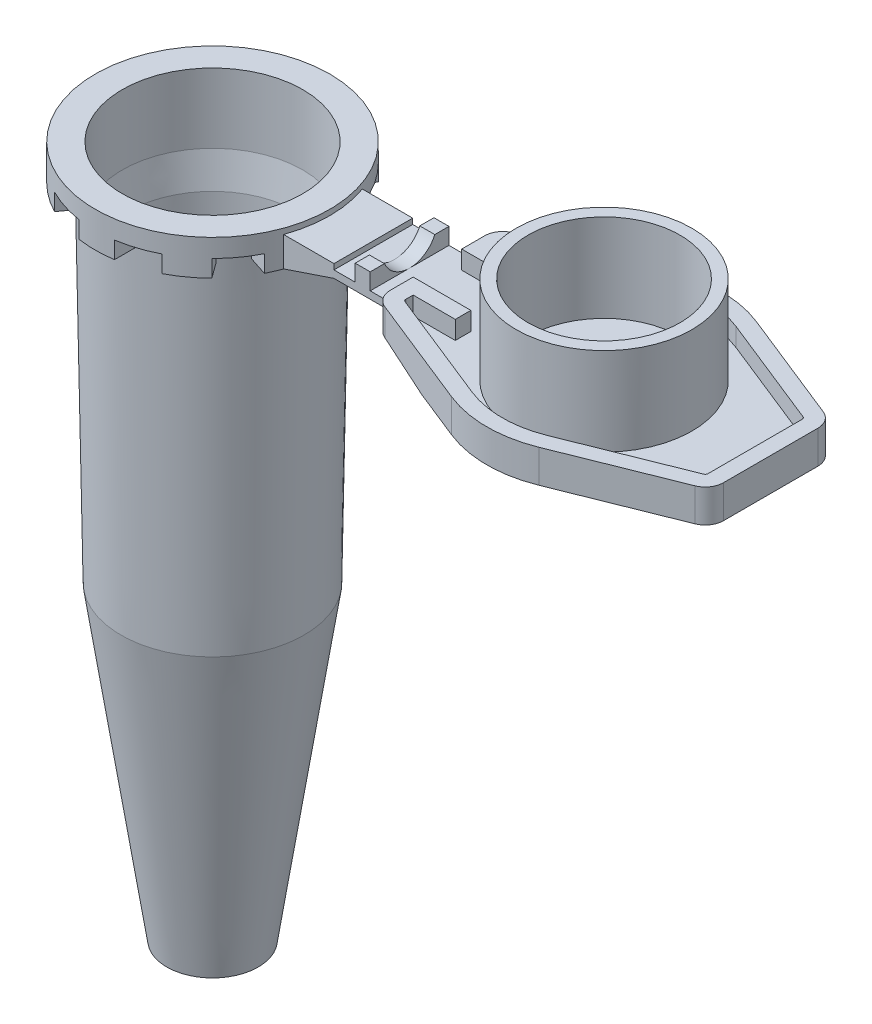
SolidWorks part; units mm, degrees
ref_plane "Front Plane" through (0, 0, 0) normal (0, 0, 1) x (1, 0, 0)
ref_plane "Top Plane" through (0, 0, 0) normal (0, 1, 0) x (1, 0, 0)
ref_plane "Right Plane" through (0, 0, 0) normal (1, 0, 0) x (0, 0, -1)
sketch "Sketch1" plane through (0, 0, 0) normal (0, 0, 1) x (1, 0, 0)
  line L0 (0, 0) -> (0, 43.428) construction
  line L1 (0, 38.64) -> (-6.405, 38.64)
  line L2 (-6.405, 38.64) -> (-6.405, 37.64)
  line L3 (-6.405, 37.64) -> (-5.325, 37.64)
  line L4 (-5.325, 37.64) -> (-5, 17.8)
  line L5 (-5, 17.8) -> (-2.5, 0.85)
  line L7 (0, 38.64) -> (0, 0)
  line L8 (-18.3321, 0.85) -> (18.9529, 0.85) construction
  arc A0 (-2.5, 0.85) -> (0, 0) centre (0, 4.1015) ccw
  point P12 (-2.5, 0.85)
  point P13 (2.5, 0.85)
  dimension "D7" = 5
  dimension "D1" = 38.64
  dimension "D2" = 12.81
  dimension "D3" = 17.8
  dimension "D4" = 10
  dimension "D5" = 10.65
  dimension "D6" = 1
  dimension "D10" = 1.7
revolve "Revolve1" add sketch "Sketch1" angle 360 about L0
sketch "Sketch2" plane through (0, 0, 0) normal (0, 0, 1) x (1, 0, 0)
  line L0 (0, 0.8) -> (0, 41.0311) construction
  line L2 (6.405, 38.64) -> (-6.405, 38.64) construction
  line L3 (-4.6, 33.04) -> (-4.25, 18.44)
  line L5 (0, 38.64) -> (0, 0) construction
  line L7 (-4.25, 18.44) -> (-1.9986, 2.5356)
  line L10 (0, 0.8) -> (4.8244, 0.8) construction
  line L16 (-4.93, 38.64) -> (-4.93, 34.84)
  line L17 (0, 38.64) -> (-6.405, 38.64) construction
  line L19 (0, 0.8) -> (0, 38.64)
  line L20 (0, 38.64) -> (-4.93, 38.64)
  line L21 (-4.6, 33.04) -> (-4.93, 34.84)
  arc A6 (-1.9986, 2.5356) -> (0, 0.8) centre (0, 2.8185) ccw
  point P0 (-3.5705, 13.64)
  point P2 (-4, 16.674)
  point P4 (-1.901, 2.14)
  point P12 (-4.8789, 44.6737)
  dimension "D1" = 9.86
  dimension "D2" = 9.2
  dimension "D3" = 8.5
  dimension "D4" = 0.8
  dimension "D5" = 25
  dimension "D6" = 9.7578
  dimension "D7" = 8
  dimension "D8" = 3.8
  dimension "D9" = 5.6
  dimension "D10" = 20.2
  dimension "D11" = 21.966
  dimension "D12" = 7.141
  dimension "D13" = 36.1044
  dimension "D14" = 36.5
  dimension "D15" = 3.8021
other "AlignGroup1"
revolve "Cut-Revolve1" cut sketch "Sketch2" angle 360 about L0
sketch "Sketch3" plane through (0, 37.64, 0) normal (0, -1, 0) x (1, 0, 0)
  line L0 (-0.975, 6.3304) -> (-0.975, 5.235)
  line L1 (0, 0) -> (0, 7.664) construction
  line L2 (0.975, 6.3304) -> (0.975, 5.235)
  circle A0 centre (0, 0) radius 5.325 construction
  arc A1 (0.975, 5.235) -> (-0.975, 5.235) centre (0, 0) ccw
  circle A2 centre (0, 0) radius 6.405 construction
  arc A3 (0.975, 6.3304) -> (-0.975, 6.3304) centre (0, 0) ccw
  dimension "D1" = 1.95
extrude "Boss-Extrude1" add sketch "Sketch3" along normal offset from surface (0.93 mm away) 1.93 up to face at (0, 38.64, -4.93)
pattern_circular "CirPattern1" count 10 over 360 about axis through (0, 38.64, 0) along (0, -1, 0) of "Boss-Extrude1"
sketch "Sketch5" plane through (0, 36.71, 0) normal (0, -1, 0) x (1, 0, 0)
  line L0 (-6.1167, 1.9) -> (-5.0895, 1.5662)
  line L1 (-6.1167, -1.9) -> (-5.0895, -1.5662)
  line L2 (0, 0) -> (-8.3672, 0) construction
  line L3 (-6.3218, 1.0289) -> (-5.2801, 0.6904) construction
  arc A0 (-5.7192, 2.8835) -> (-6.3218, 1.0289) centre (0, 0) ccw construction
  arc A1 (-4.6775, 2.545) -> (-5.2801, 0.6904) centre (0, 0) ccw construction
  arc A2 (-6.3218, -1.0289) -> (-5.7192, -2.8835) centre (0, 0) ccw construction
  arc A3 (-5.2801, -0.6904) -> (-4.6775, -2.545) centre (0, 0) ccw construction
  arc A4 (-5.0895, 1.5662) -> (-5.0895, -1.5662) centre (0, 0) ccw
  arc A5 (-6.1167, 1.9) -> (-6.1167, -1.9) centre (0, 0) ccw
  dimension "D1" = 3.8
extrude "Cut-Extrude1" cut sketch "Sketch5" against normal up to surface (0.93 mm away) up to face at (-5.833, 37.64, 0)
sketch "Sketch6" plane through (0, 37.64, 0) normal (0, -1, 0) x (1, 0, 0)
  line L0 (0, 0) -> (15.5128, 0) construction
  line L1 (6.0334, 2.15) -> (12.2834, 2.15)
  line L3 (6.0334, -2.15) -> (12.2834, -2.15)
  line L4 (12.2834, 2.15) -> (12.2834, -2.15)
  circle A0 centre (0, 0) radius 6.405 construction
  arc A1 (6.0334, -2.15) -> (6.0334, 2.15) centre (0, 0) ccw
  dimension "D1" = 4.3
  dimension "D2" = 6.25
extrude "Boss-Extrude2" add sketch "Sketch6" against normal blind 0.4
sketch "Sketch7" plane through (0, 0, -2.15) normal (0, 0, -1) x (-1, 0, 0)
  line L0 (-6.0334, 38.04) -> (-6.0334, 38.34)
  line L1 (-6.0334, 38.34) -> (-8.7834, 38.34)
  line L2 (-8.7834, 38.34) -> (-8.7834, 38.04)
  line L3 (-6.0334, 38.04) -> (-12.2834, 38.04) construction
  line L4 (-8.7834, 38.04) -> (-6.0334, 38.04)
  dimension "D1" = 2.75
  dimension "D2" = 0.3
extrude "Boss-Extrude3" add sketch "Sketch7" against normal up to surface (4.3 mm away) up to face at (9.1584, 37.84, 2.15)
sketch "Sketch8" plane through (0, 0, -2.15) normal (0, 0, -1) x (-1, 0, 0)
  line L0 (-6.0334, 37.64) -> (-6.0205, 36.71)
  line L1 (-6.3218, 36.71) -> (-5.7192, 36.71) construction
  line L2 (-6.0205, 36.71) -> (-8.7834, 37.64)
  line L3 (-8.7834, 38.34) -> (-8.7834, 38.04) construction
  line L4 (-6.0334, 37.64) -> (-12.2834, 37.64) construction
  line L5 (-8.7834, 37.64) -> (-6.0334, 37.64)
extrude "Boss-Extrude4" add sketch "Sketch8" against normal blind 0.8
mirror "Mirror1" about plane through (0, 0, 0) normal (0, 0, 1) of "Boss-Extrude4"
sketch "Sketch9" plane through (0, 0, -2.15) normal (0, 0, -1) x (-1, 0, 0)
  line L0 (-8.7834, 38.04) -> (-12.2834, 38.04) construction
  line L1 (-9.9434, 38.04) -> (-10.7634, 38.04)
  line L2 (-9.9434, 38.04) -> (-9.9434, 38.94)
  line L3 (-9.9434, 38.94) -> (-10.7634, 38.94)
  line L4 (-10.7634, 38.04) -> (-10.7634, 38.94)
  line L5 (-8.7834, 38.34) -> (-8.7834, 38.04) construction
  line L6 (-8.7834, 37.64) -> (-12.2834, 37.64) construction
  dimension "D1" = 1.16
  dimension "D2" = 0.82
  dimension "D3" = 1.3
extrude "Boss-Extrude5" add sketch "Sketch9" against normal up to surface (4.3 mm away) up to face at (8.9977, 37.822, 2.15)
sketch "Sketch10" plane through (10.7634, 0, 0) normal (1, 0, 0) x (0, 0, -1)
  line L0 (-2.15, 38.04) -> (2.15, 38.04) construction
  line L1 (0, 38.94) -> (0, 42.66) construction
  line L2 (-2.15, 38.94) -> (2.15, 38.94) construction
  circle A0 centre (0, 39.54) radius 1.5
  dimension "D1" = 3
extrude "Cut-Extrude2" cut sketch "Sketch10" against normal up to surface (0.82 mm away) up to face at (9.9434, 38.49, 0)
sketch "Sketch11" plane through (0, 38.04, 0) normal (0, 1, 0) x (1, 0, 0)
  line L0 (12.2834, 0) -> (30.4834, 0) construction
  line L1 (12.2834, 2.15) -> (12.2834, -2.15) construction
  line L2 (21.3834, 6.4) -> (21.3834, -6.4) construction
  line L3 (12.2834, 3.25) -> (12.2834, -3.25)
  line L4 (12.2834, -3.25) -> (19.0042, -5.9413)
  line L5 (12.2834, 3.25) -> (19.0042, 5.9413)
  line L6 (30.4834, 3.25) -> (23.7626, 5.9413)
  line L7 (30.4834, -3.25) -> (23.7626, -5.9413)
  line L8 (30.4834, 3.25) -> (30.4834, -3.25)
  arc A0 (19.0042, -5.9413) -> (23.7626, -5.9413) centre (21.3834, 0) ccw
  arc A1 (23.7626, 5.9413) -> (19.0042, 5.9413) centre (21.3834, 0) ccw
  point P7 (21.3834, 0)
  point P10 (21.3834, 0)
  dimension "D1" = 18.2
  dimension "D2" = 12.8
  dimension "D3" = 6.5
extrude "Boss-Extrude6" add sketch "Sketch11" against normal blind 0.8
sketch "Sketch12" plane through (0, 0, 0) normal (0, 0, 1) x (1, 0, 0)
  line L0 (12.2834, 37.64) -> (16.2834, 37.24)
  line L1 (12.2834, 37.24) -> (19.0042, 37.24) construction
  line L2 (12.2834, 37.64) -> (12.2834, 37.24)
  line L3 (12.2834, 37.24) -> (16.2834, 37.24)
  dimension "D1" = 4
extrude "Cut-Extrude3" cut sketch "Sketch12" against normal through all and the other way through all
fillet "Fillet1" radius 1 4 edges at (30.4834, 37.64, -3.25) (30.4834, 37.64, 3.25) (12.2834, 37.84, -3.25) (12.2834, 37.84, 3.25)
sketch "Sketch13" plane through (0, 38.04, 0) normal (0, 1, 0) x (1, 0, 0)
  circle A0 centre (21.3834, 0) radius 4.8
  circle A1 centre (21.3834, 0) radius 4.15
  dimension "D1" = 9.6
  dimension "D2" = 8.3
extrude "Boss-Extrude7" add sketch "Sketch13" along normal blind 4.8
sketch "Sketch14" plane through (0, 38.04, 0) normal (0, 1, 0) x (1, 0, 0)
  line L0 (12.2834, 2.5732) -> (12.2834, 2.15) construction
  line L1 (19.0042, 5.9413) -> (12.9116, 3.5016) construction
  line L2 (29.8551, 3.5016) -> (23.7626, 5.9413) construction
  line L3 (30.4834, -2.5732) -> (30.4834, 2.5732) construction
  line L4 (23.7626, -5.9413) -> (29.8551, -3.5016) construction
  line L5 (12.2834, -2.15) -> (12.2834, -2.5732) construction
  line L6 (12.9116, -3.5016) -> (19.0042, -5.9413) construction
  line L7 (12.2834, 2.5732) -> (12.2834, 2.15)
  line L8 (19.0042, 5.9413) -> (12.9116, 3.5016)
  line L9 (29.8551, 3.5016) -> (23.7626, 5.9413)
  line L10 (30.4834, -2.5732) -> (30.4834, 2.5732)
  line L11 (23.7626, -5.9413) -> (29.8551, -3.5016)
  line L12 (12.2834, -2.15) -> (12.2834, -2.5732)
  line L13 (12.9116, -3.5016) -> (19.0042, -5.9413)
  line L14 (12.2834, -2.15) -> (12.2834, -1.325)
  line L15 (12.2834, -1.325) -> (15.4334, -1.325)
  line L16 (21.3834, 0) -> (7.7654, 0) construction
  line L17 (12.2834, 1.325) -> (15.4334, 1.325)
  line L18 (12.2834, 2.15) -> (12.2834, 1.325)
  line L19 (13.1334, 2.175) -> (15.4334, 2.175)
  line L20 (13.1334, 2.175) -> (13.1334, 2.175)
  line L21 (13.1334, 2.5732) -> (13.1334, 2.175)
  line L22 (19.3202, 5.1522) -> (13.2276, 2.7125)
  line L23 (29.5391, 2.7125) -> (23.4466, 5.1522)
  line L24 (29.6334, -2.5732) -> (29.6334, 2.5732)
  line L25 (23.4466, -5.1522) -> (29.5391, -2.7125)
  line L26 (13.2276, -2.7125) -> (19.3202, -5.1522)
  line L27 (13.1334, -2.175) -> (13.1334, -2.5732)
  line L28 (13.1334, -2.175) -> (13.1334, -2.175)
  line L29 (13.1334, -2.175) -> (15.4334, -2.175)
  line L30 (15.4334, -2.175) -> (15.4334, -1.325)
  line L31 (15.4334, 1.325) -> (15.4334, 2.175)
  arc A0 (12.9116, 3.5016) -> (12.2834, 2.5732) centre (13.2834, 2.5732) ccw construction
  arc A1 (23.7626, 5.9413) -> (19.0042, 5.9413) centre (21.3834, 0) ccw construction
  arc A2 (30.4834, 2.5732) -> (29.8551, 3.5016) centre (29.4834, 2.5732) ccw construction
  arc A3 (29.8551, -3.5016) -> (30.4834, -2.5732) centre (29.4834, -2.5732) ccw construction
  arc A4 (19.0042, -5.9413) -> (23.7626, -5.9413) centre (21.3834, 0) ccw construction
  arc A5 (12.2834, -2.5732) -> (12.9116, -3.5016) centre (13.2834, -2.5732) ccw construction
  arc A6 (12.9116, 3.5016) -> (12.2834, 2.5732) centre (13.2834, 2.5732) ccw
  arc A7 (23.7626, 5.9413) -> (19.0042, 5.9413) centre (21.3834, 0) ccw
  arc A8 (30.4834, 2.5732) -> (29.8551, 3.5016) centre (29.4834, 2.5732) ccw
  arc A9 (29.8551, -3.5016) -> (30.4834, -2.5732) centre (29.4834, -2.5732) ccw
  arc A10 (19.0042, -5.9413) -> (23.7626, -5.9413) centre (21.3834, 0) ccw
  arc A11 (12.2834, -2.5732) -> (12.9116, -3.5016) centre (13.2834, -2.5732) ccw
  arc A12 (13.2276, 2.7125) -> (13.1334, 2.5732) centre (13.2834, 2.5732) ccw
  arc A13 (23.4466, 5.1522) -> (19.3202, 5.1522) centre (21.3834, 0) ccw
  arc A14 (29.6334, 2.5732) -> (29.5391, 2.7125) centre (29.4834, 2.5732) ccw
  arc A15 (29.5391, -2.7125) -> (29.6334, -2.5732) centre (29.4834, -2.5732) ccw
  arc A16 (19.3202, -5.1522) -> (23.4466, -5.1522) centre (21.3834, 0) ccw
  arc A17 (13.1334, -2.5732) -> (13.2276, -2.7125) centre (13.2834, -2.5732) ccw
  point P24 (13.8584, 1.325)
  dimension "D1" = 2.65
  dimension "D2" = 3.15
  dimension "D3" = 0.85
extrude "Boss-Extrude8" add sketch "Sketch14" along normal blind 1
ref_plane "Lid Closure Plane" through (0, 35.04, 0) normal (0, 1, 0) x (1, 0, 0)
ref_axis "Axis1" through (0, 37.64, 0) along (0, -1, 0)
ref_plane "Plane1" through (0, 10, 0) normal (0, 1, 0) x (1, 0, 0)
ref_point "FocalPoint"
